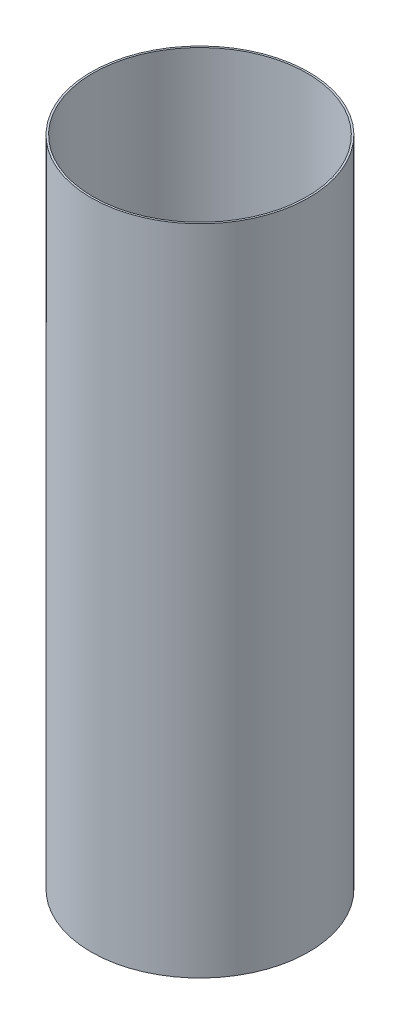
SolidWorks part; units mm, degrees
ref_plane "Front Plane" through (0, 0, 0) normal (0, 0, 1) x (1, 0, 0)
ref_plane "Top Plane" through (0, 0, 0) normal (0, 1, 0) x (1, 0, 0)
ref_plane "Right Plane" through (0, 0, 0) normal (1, 0, 0) x (0, 0, -1)
sketch "Sketch1" plane through (0, 0, 0) normal (0, 1, 0) x (1, 0, 0)
  circle A0 centre (0, 0) radius 76.2
  dimension "D1" = 152.4
extrude "Boss-Extrude1" add sketch "Sketch1" along normal blind 457.2
sketch "Sketch2" plane through (0, 457.2, 0) normal (0, 1, 0) x (1, 0, 0)
  circle A0 centre (0, 0) radius 74.93
  dimension "D1" = 149.86
extrude "Cut-Extrude1" cut sketch "Sketch2" against normal through all
